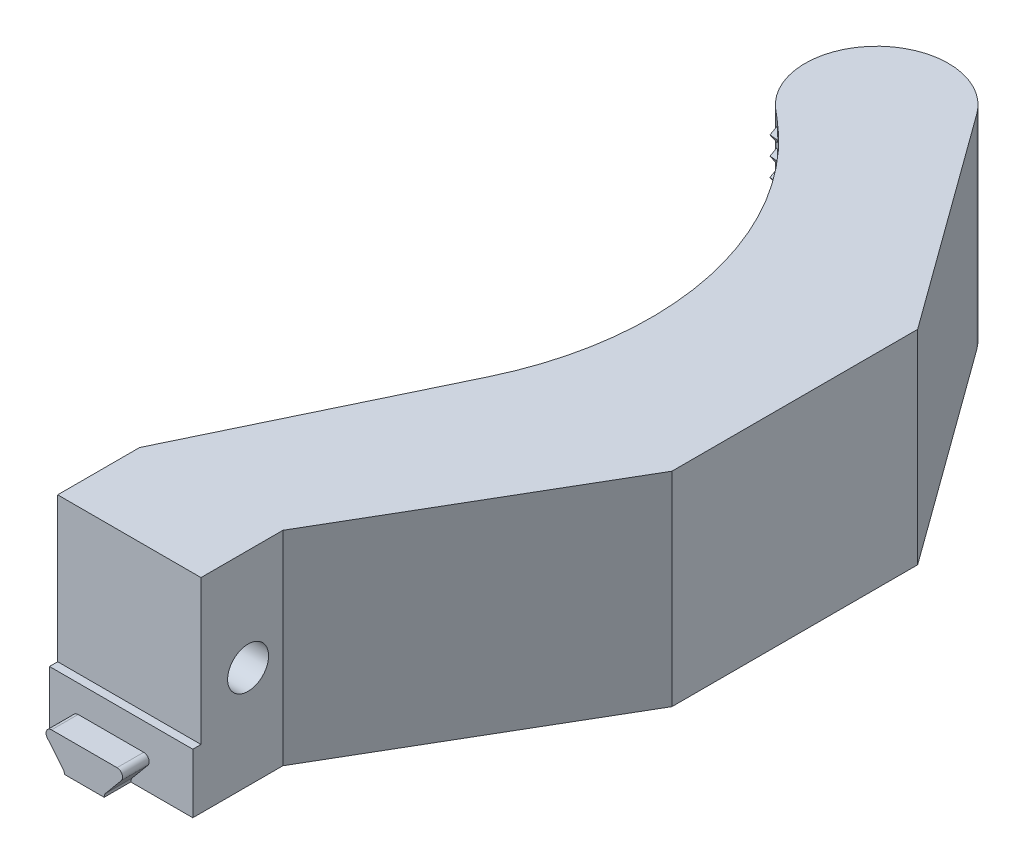
SolidWorks part; units mm, degrees
ref_plane "Front Plane" through (0, 0, 0) normal (0, 0, 1) x (1, 0, 0)
ref_plane "Top Plane" through (0, 0, 0) normal (0, 1, 0) x (1, 0, 0)
ref_plane "Right Plane" through (0, 0, 0) normal (1, 0, 0) x (0, 0, -1)
sketch "Sketch1" plane through (0, 0, 0) normal (0, 0, 1) x (1, 0, 0)
  line L1 (0, 0) -> (-35, 0)
  line L2 (0, 0) -> (0, 14.5)
  line L4 (-35, 0) -> (-35, 14.5)
  line L9 (0, 14.5) -> (-35, 14.5)
  dimension "D2" = 35
  dimension "D3" = 14.5
extrude "Offset" add sketch "Sketch1" along normal blind 2
sketch "Sketch13" plane through (0, 0, 2) normal (0, 0, 1) x (1, 0, 0)
  line L3 (-24.85, 0) -> (-15.15, 0)
  line L6 (-25.2309, 1.0544) -> (-29.0384, 5.6373)
  line L7 (-28, 7.85) -> (-12, 7.85)
  line L8 (-10.9616, 5.6373) -> (-14.7691, 1.0544)
  line L9 (-25.2309, 1.0544) -> (-29.0384, 5.6373)
  line L10 (-28, 7.85) -> (-12, 7.85)
  line L11 (-10.9616, 5.6373) -> (-14.7691, 1.0544)
  arc A8 (-14.7691, 1.0544) -> (-15.15, 0) centre (-13.5, 0) ccw
  arc A9 (-24.85, 0) -> (-25.2309, 1.0544) centre (-26.5, 0) ccw
  arc A10 (-28, 7.85) -> (-29.0384, 5.6373) centre (-28, 6.5) ccw
  arc A11 (-10.9616, 5.6373) -> (-12, 7.85) centre (-12, 6.5) ccw
  arc A12 (-14.7691, 1.0544) -> (-15.15, 0) centre (-13.5, 0) ccw
  arc A13 (-24.85, 0) -> (-25.2309, 1.0544) centre (-26.5, 0) ccw
  arc A14 (-28, 7.85) -> (-29.0384, 5.6373) centre (-28, 6.5) ccw
  arc A15 (-10.9616, 5.6373) -> (-12, 7.85) centre (-12, 6.5) ccw
  dimension "D1" = 0.15
extrude "Dovetail" add sketch "Sketch13" along normal up to surface (6.5 mm away)
sketch "Sketch5" plane through (0, 0, 0) normal (0, 0, -1) x (-1, 0, 0)
  line L0 (35, 14.5) -> (35, 0) construction
  line L1 (0, 0) -> (35, 0)
  line L2 (0, 0) -> (0, 49.8)
  line L3 (0, 49.8) -> (35, 49.8)
  line L4 (35, 0) -> (35, 49.8)
  line L5 (0, 0) -> (35, 49.8) construction
  line L6 (0, 49.8) -> (35, 0) construction
  line L7 (101.8959, 50) -> (-19.1041, 50) construction
  point P4 (17.5, 24.9)
  dimension "D1" = 0.2
extrude "Base" add sketch "Sketch5" along normal blind 20
sketch "Sketch6" plane through (0, 0, 0) normal (0, -1, 0) x (1, 0, 0)
  line L4 (-35, -20) -> (0, -20)
  line L6 (-28.7409, -169.0876) -> (-26.8248, -167.4818)
  line L7 (-7.3824, -77.5523) -> (-35, -20)
  line L9 (0, -20) -> (35, -80)
  line L10 (35, -80) -> (35, -140)
  line L11 (35, -140) -> (-3.341, -192.7846)
  arc A2 (-28.7409, -169.0876) -> (-3.341, -192.7846) centre (-17.5, -182.5) ccw
  arc A3 (-26.8248, -167.4818) -> (-7.3824, -77.5523) centre (-75, -110) ccw
  point P5 (35, -110)
  point P11 (-17.5, -20)
  dimension "D1" = 75
  dimension "D3" = 35
  dimension "D2" = 35
  dimension "D4" = 90
  dimension "D5" = 180
  dimension "D6" = 60
  dimension "D7" = 35
  dimension "D8" = 40
extrude "Gripping" add sketch "Sketch6" against normal up to surface (49.8 mm away) up to face at (-17.5, 49.8, -10)
sketch "Sketch7" plane through (73.5161, 0, -83.3865) normal (-0.6423, 0, 0.7664) x (0.7664, 0, 0.6423)
  line L0 (-132.421, 46.5322) -> (-130.6532, 44.7645)
  line L1 (-132.421, 46.5322) -> (-130.6532, 48.3)
  line L2 (-130.6532, 44.7645) -> (-128.8854, 46.5322)
  line L3 (-130.6532, 48.3) -> (-128.8854, 46.5322)
  line L4 (-42.4538, 49.8) -> (-29.6071, 49.8) construction
  line L5 (-133.421, 49.8) -> (-133.421, 0) construction
  dimension "D1" = 135
  dimension "D2" = 2.5
  dimension "D3" = 1.5
  dimension "D4" = 1
extrude "Texture" add sketch "Sketch7" along normal blind 2 draft 45
pattern_linear "LPattern1" count 1 spacing 4.5 along (-0.7664, 0, -0.6423) count 11 spacing 4.5 along (0, -1, 0) of "Texture"
sketch "Sketch15" plane through (-37.4536, 0, -14.8869) normal (-0.9016, 0, -0.4326) x (-0.4326, 0, 0.9016)
  line L0 (-68.5071, 46.5322) -> (-66.7393, 44.7645)
  line L1 (-68.5071, 46.5322) -> (-66.7393, 48.3)
  line L2 (-66.7393, 44.7645) -> (-64.9716, 46.5322)
  line L3 (-66.7393, 48.3) -> (-64.9716, 46.5322)
  line L6 (-69.5071, 49.8) -> (-5.6714, 49.8) construction
  line L7 (-69.5071, 49.8) -> (-69.5071, 0) construction
  dimension "D1" = 1.5
  dimension "D2" = 2.5
  dimension "D3" = 1
extrude "Texture 2" add sketch "Sketch15" along normal blind 2 draft 45
pattern_linear "LPattern2" count 14 spacing 4.5 along (-0.4326, 0, 0.9016) count 11 spacing 4.5 along (0, -1, 0) of "Texture 2"
sketch "Sketch11" plane through (-35, 0, 0) normal (-1, 0, 0) x (0, 0, 1)
  line L1 (13, 50) -> (13, 0) construction
  line L7 (-21, 50) -> (8.5, 50) construction
  line L8 (-21, 0) -> (8.5, 0) construction
  circle A0 centre (-11.5, 25) radius 5
  circle A2 centre (-11.5, 25) radius 2.55 construction
  point P6 (13, 25)
  dimension "D1" = 10
extrude "ShaftHole" cut sketch "Sketch11" against normal through all both and the other way through all
equation "\"D3@Sketch6\"=\"D2@Sketch6\""
equation "\"D5@Sketch6\"=2*\"D4@Sketch6\""
